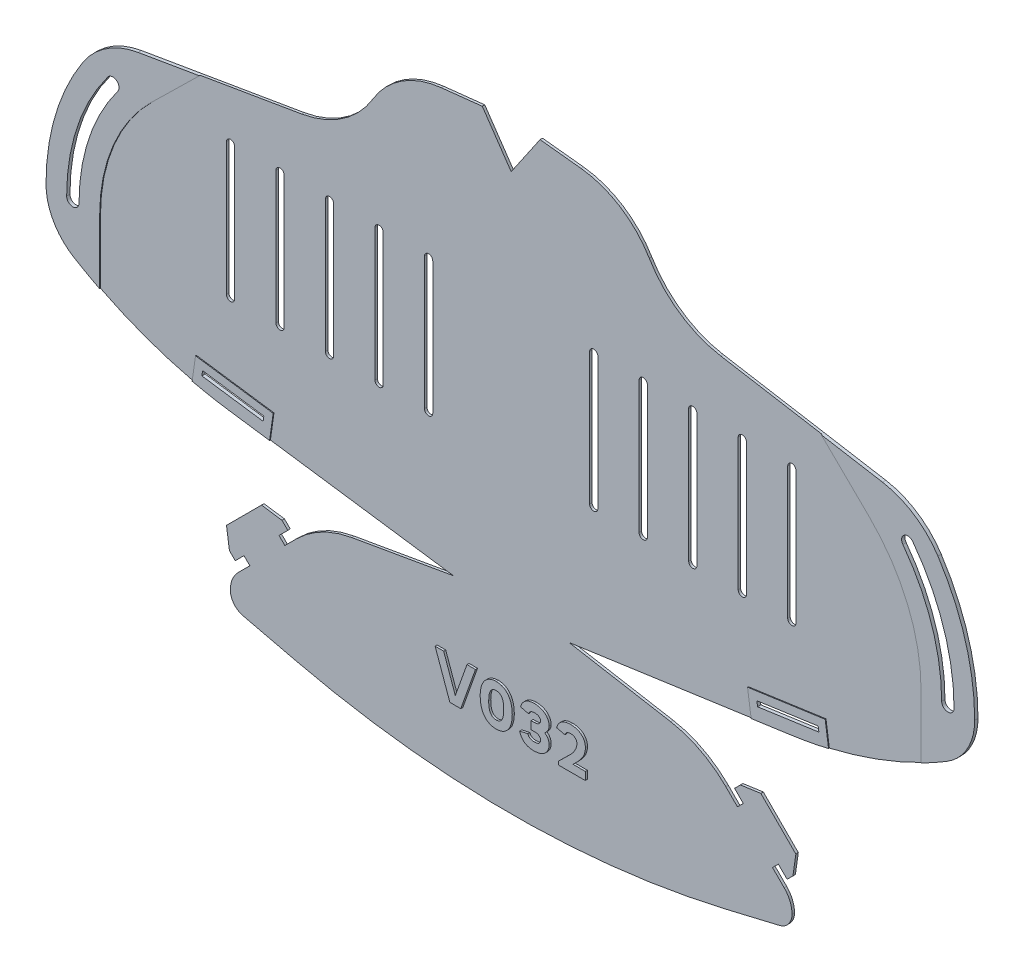
SolidWorks part; units mm, degrees
ref_plane "Front Plane" through (0, 0, 0) normal (0, 0, 1) x (1, 0, 0)
ref_plane "Top Plane" through (0, 0, 0) normal (0, 1, 0) x (1, 0, 0)
ref_plane "Right Plane" through (0, 0, 0) normal (1, 0, 0) x (0, 0, -1)
sketch "Sketch1" plane through (0, 0, 0) normal (0, 0, 1) x (1, 0, 0)
  line L0 (0, 0) -> (0, -145) construction
  line L1 (-14, -102) -> (14, -102) construction
  line L2 (-112.5, -69) -> (112.5, -69) construction
  line L3 (0, -10.2352) -> (-7, 0)
  line L4 (0, -10.2352) -> (7, 0)
  line L5 (7, 0) -> (16.9419, -1.0768)
  line L6 (-90.1804, -30.1909) -> (-50.7439, -23.5)
  line L7 (90.1804, -30.1909) -> (50.7439, -23.5)
  line L8 (-14, -102) -> (-68.2662, -94.2919)
  line L9 (-7, 0) -> (-16.9419, -1.0768)
  line L10 (14, -102) -> (68.2662, -94.2919)
  line L11 (-103.5977, -39) -> (-103.5977, -69) construction
  line L12 (-14, -102) -> (-38.6266, -106.305)
  line L13 (-52, -113.2546) -> (-54.8283, -116.0832)
  line L14 (52, -113.2546) -> (54.8283, -116.0832)
  line L15 (14, -102) -> (38.6266, -106.305)
  line L16 (-54.8283, -116.0832) -> (-56.2426, -114.669)
  line L17 (-56.2426, -114.669) -> (-54.1214, -112.5476)
  line L18 (-54.1214, -112.5476) -> (-55.5356, -111.1334)
  line L19 (-55.5356, -111.1334) -> (-60.4854, -110.4265)
  line L20 (-60.4854, -110.4265) -> (-68.9703, -118.9122)
  line L21 (-64.7275, -123.1546) -> (-63.3132, -124.5688)
  line L22 (-63.3132, -124.5688) -> (-66.1415, -127.3973)
  line L23 (-64.7275, -123.1546) -> (-66.8487, -125.2761)
  line L24 (-66.8487, -125.2761) -> (-68.263, -123.8619)
  line L25 (-68.9703, -118.9122) -> (-68.263, -123.8619)
  line L26 (68.9703, -118.9122) -> (68.263, -123.8619)
  line L27 (66.8487, -125.2761) -> (68.263, -123.8619)
  line L28 (64.7275, -123.1546) -> (66.8487, -125.2761)
  line L29 (63.3132, -124.5688) -> (66.1415, -127.3973)
  line L30 (64.7275, -123.1546) -> (63.3132, -124.5688)
  line L31 (60.4854, -110.4265) -> (68.9703, -118.9122)
  line L32 (55.5356, -111.1334) -> (60.4854, -110.4265)
  line L33 (54.1214, -112.5476) -> (55.5356, -111.1334)
  line L34 (56.2426, -114.669) -> (54.1214, -112.5476)
  line L35 (54.8283, -116.0832) -> (56.2426, -114.669)
  line L36 (-64.9691, -135.8852) -> (-52.4361, -138.8607)
  line L37 (64.9691, -135.8852) -> (52.4361, -138.8607)
  line L38 (-68.9703, -118.9122) -> (-64.7275, -123.1546) construction
  line L39 (-60.4854, -110.4265) -> (-56.2426, -114.669) construction
  arc A0 (-16.9419, -1.0768) -> (-33.4614, -11.6696) centre (-14.5729, -22.9489) ccw
  arc A1 (-33.4614, -11.6696) -> (-50.7439, -23.5) centre (-54.9257, 1.1478) cw
  arc A2 (-103.5977, -39) -> (-90.1804, -30.1909) centre (-86.8349, -49.9091) cw
  arc A3 (-112.5, -69) -> (-103.5977, -39) centre (-57.5, -69) cw
  arc A4 (112.5, -69) -> (103.5977, -39) centre (57.5, -69) ccw
  arc A5 (103.5977, -39) -> (90.1804, -30.1909) centre (86.8349, -49.9091) ccw
  arc A6 (16.9419, -1.0768) -> (33.4614, -11.6696) centre (14.5729, -22.9489) cw
  arc A7 (33.4614, -11.6696) -> (50.7439, -23.5) centre (54.9257, 1.1478) ccw
  arc A8 (-112.5, -69) -> (-105.7111, -81) centre (-98.5, -69) ccw
  arc A9 (-105.7111, -81) -> (-68.2662, -94.2919) centre (-54.2032, 4.7143) ccw
  arc A10 (112.5, -69) -> (105.7111, -81) centre (98.5, -69) cw
  arc A11 (105.7111, -81) -> (68.2662, -94.2919) centre (54.2032, 4.7143) cw
  arc A12 (-38.6266, -106.305) -> (-52, -113.2546) centre (-34.3216, -130.9315) ccw
  arc A13 (38.6266, -106.305) -> (52, -113.2546) centre (34.3216, -130.9315) cw
  arc A14 (-66.1415, -127.3973) -> (-68.0451, -131.9933) centre (-61.5451, -131.9933) ccw
  arc A15 (-68.0451, -131.9933) -> (-64.9691, -135.8852) centre (-64.0451, -131.9933) ccw
  arc A16 (68.0451, -131.9933) -> (64.9691, -135.8852) centre (64.0451, -131.9933) cw
  arc A17 (66.1415, -127.3973) -> (68.0451, -131.9933) centre (61.5451, -131.9933) cw
  arc A19 (-52.4361, -138.8607) -> (0, -145) centre (0, 82) ccw
  arc A20 (52.4361, -138.8607) -> (0, -145) centre (0, 82) cw
  point P8 (0, -102)
  point P11 (0, -69)
  dimension "D5" = 55
  dimension "D11" = 20
  dimension "D13" = 25
  dimension "D16" = 14
  dimension "D15" = 22
  dimension "D18" = 100
  dimension "D22" = 25
  dimension "D31" = 6.5
  dimension "D32" = 4
  dimension "D34" = 227
  dimension "D1" = 145
  dimension "D2" = 28
  dimension "D3" = 43
  dimension "D4" = 76
  dimension "D6" = 225
  dimension "D7" = 14
  dimension "D8" = 12.4
  dimension "D9" = 10
  dimension "D10" = 30
  dimension "D12" = 40
  dimension "D14" = 45.5
  dimension "D17" = 12
  dimension "D19" = 18
  dimension "D20" = 25
  dimension "D21" = 4
  dimension "D23" = 38
  dimension "D24" = 2
  dimension "D25" = 3
  dimension "D26" = 2
  dimension "D27" = 18
  dimension "D29" = 8
  dimension "D30" = 4
extrude "Main Shape" add sketch "Sketch1" along normal blind 0.6
sketch "Sketch2" plane through (0, 0, 0.6) normal (0, 0, 1) x (1, 0, 0)
  line L0 (0, -55) -> (0, 55) construction
  arc A0 (-96.3, -39.9) -> (-106, -69) centre (-57.5, -69) ccw construction
  arc A1 (-97.5, -39) -> (-107.5, -69) centre (-57.5, -69) ccw
  arc A2 (-95.1, -40.8) -> (-104.5, -69) centre (-57.5, -69) ccw
  arc A3 (-95.1, -40.8) -> (-97.5, -39) centre (-96.3, -39.9) ccw
  arc A4 (-107.5, -69) -> (-104.5, -69) centre (-106, -69) ccw
  arc A6 (-103.5977, -39) -> (-112.5, -69) centre (-57.5, -69) ccw construction
  arc A7 (96.3, -39.9) -> (106, -69) centre (57.5, -69) cw construction
  arc A8 (97.5, -39) -> (107.5, -69) centre (57.5, -69) cw
  arc A9 (95.1, -40.8) -> (104.5, -69) centre (57.5, -69) cw
  arc A10 (95.1, -40.8) -> (97.5, -39) centre (96.3, -39.9) cw
  arc A11 (107.5, -69) -> (104.5, -69) centre (106, -69) cw
  point P3 (-103.5111, -53.663)
  point P19 (103.5111, -53.663)
  dimension "D1" = 5
  dimension "D2" = 1.5
extrude "Elastic Attachment Points" cut sketch "Sketch2" against normal through all
sketch "Sketch7" plane through (0, 0, 0.6) normal (0, 0, 1) x (1, 0, 0)
  line L0 (-99.5, -69) -> (-99.5, -84.4384)
  line L1 (-86.8939, -39) -> (-75.3319, -27.6717)
  line L2 (-50.7439, -23.5) -> (-90.1804, -30.1909) construction
  line L3 (-75.3319, -27.6717) -> (-90.1804, -30.1909)
  line L4 (0, -55) -> (0, 55) construction
  line L5 (75.3319, -27.6717) -> (90.1804, -30.1909)
  line L6 (86.8939, -39) -> (75.3319, -27.6717)
  line L7 (99.5, -69) -> (99.5, -84.4384)
  arc A0 (-99.5, -69) -> (-86.8939, -39) centre (-57.5, -69) cw
  arc A1 (-95.1, -40.8) -> (-104.5, -69) centre (-57.5, -69) ccw construction
  arc A2 (-105.7111, -81) -> (-68.2662, -94.2919) centre (-54.2032, 4.7143) ccw construction
  arc A3 (-112.5, -69) -> (-105.7111, -81) centre (-98.5, -69) ccw construction
  arc A4 (-103.5977, -39) -> (-112.5, -69) centre (-57.5, -69) ccw construction
  arc A5 (-90.1804, -30.1909) -> (-103.5977, -39) centre (-86.8349, -49.9091) ccw construction
  arc A6 (-105.7111, -81) -> (-99.5, -84.4384) centre (-54.2032, 4.7143) ccw
  arc A7 (-112.5, -69) -> (-105.7111, -81) centre (-98.5, -69) ccw
  arc A8 (-103.5977, -39) -> (-112.5, -69) centre (-57.5, -69) ccw
  arc A9 (-90.1804, -30.1909) -> (-103.5977, -39) centre (-86.8349, -49.9091) ccw
  arc A10 (90.1804, -30.1909) -> (103.5977, -39) centre (86.8349, -49.9091) cw
  arc A11 (103.5977, -39) -> (112.5, -69) centre (57.5, -69) cw
  arc A12 (112.5, -69) -> (105.7111, -81) centre (98.5, -69) cw
  arc A13 (105.7111, -81) -> (99.5, -84.4384) centre (54.2032, 4.7143) cw
  arc A14 (99.5, -69) -> (86.8939, -39) centre (57.5, -69) ccw
  arc A15 (-107.5, -69) -> (-104.5, -69) centre (-106, -69) ccw construction
  arc A16 (-95.1, -40.8) -> (-97.5, -39) centre (-96.3, -39.9) ccw construction
  arc A17 (-97.5, -39) -> (-107.5, -69) centre (-57.5, -69) ccw construction
  arc A18 (-107.5, -69) -> (-104.5, -69) centre (-106, -69) ccw
  arc A19 (-95.1, -40.8) -> (-97.5, -39) centre (-96.3, -39.9) ccw
  arc A20 (-95.1, -40.8) -> (-104.5, -69) centre (-57.5, -69) ccw
  arc A21 (-97.5, -39) -> (-107.5, -69) centre (-57.5, -69) ccw
  arc A22 (104.5, -69) -> (107.5, -69) centre (106, -69) ccw construction
  arc A23 (97.5, -39) -> (95.1, -40.8) centre (96.3, -39.9) ccw construction
  arc A24 (104.5, -69) -> (95.1, -40.8) centre (57.5, -69) ccw construction
  arc A25 (107.5, -69) -> (97.5, -39) centre (57.5, -69) ccw construction
  arc A26 (104.5, -69) -> (107.5, -69) centre (106, -69) ccw
  arc A27 (97.5, -39) -> (95.1, -40.8) centre (96.3, -39.9) ccw
  arc A28 (104.5, -69) -> (95.1, -40.8) centre (57.5, -69) ccw
  arc A29 (107.5, -69) -> (97.5, -39) centre (57.5, -69) ccw
  dimension "D1" = 5
extrude "Reinforced Attachment Points" add sketch "Sketch7" along normal blind 0.2
sketch "Sketch6" plane through (0, 0, 0.6) normal (0, 0, 1) x (1, 0, 0)
  line L0 (-74.7442, -90.3417) -> (-59.8932, -92.4511)
  line L1 (-59.8932, -92.4511) -> (-59.7245, -91.2631)
  line L2 (-59.7245, -91.2631) -> (-74.5754, -89.1536)
  line L3 (-74.5754, -89.1536) -> (-74.7442, -90.3417)
  line L4 (-68.2662, -94.2919) -> (-14, -102) construction
  line L5 (-67.1499, -90.2083) -> (-67.3187, -91.3964) construction
  line L13 (0, -55) -> (0, 55) construction
  line L14 (67.1499, -90.2083) -> (67.3187, -91.3964) construction
  line L15 (74.7442, -90.3417) -> (74.5754, -89.1536)
  line L16 (59.7245, -91.2631) -> (59.8932, -92.4511)
  line L22 (59.7245, -91.2631) -> (74.5754, -89.1536)
  line L24 (74.7442, -90.3417) -> (59.8932, -92.4511)
  dimension "D1" = 3
  dimension "D2" = 15
  dimension "D3" = 54.28
  dimension "D4" = 1.2
extrude "Tab Slits" cut sketch "Sketch6" against normal through all
sketch "Sketch9" plane through (0, 0, 0.6) normal (0, 0, 1) x (1, 0, 0)
  line L4 (-59.8932, -92.4511) -> (-59.7245, -91.2631) construction
  line L5 (-74.7442, -90.3417) -> (-59.8932, -92.4511) construction
  line L6 (-74.5754, -89.1536) -> (-74.7442, -90.3417) construction
  line L7 (-59.7245, -91.2631) -> (-74.5754, -89.1536) construction
  line L12 (-59.8932, -92.4511) -> (-59.7245, -91.2631)
  line L13 (-74.7442, -90.3417) -> (-59.8932, -92.4511)
  line L14 (-74.5754, -89.1536) -> (-74.7442, -90.3417)
  line L15 (-59.7245, -91.2631) -> (-74.5754, -89.1536)
  line L16 (-58.335, -95.7026) -> (-57.4631, -89.5642)
  line L17 (-68.2662, -94.2919) -> (-14, -102) construction
  line L18 (-57.4631, -89.5642) -> (-76.2743, -86.8922)
  line L19 (-76.2743, -86.8922) -> (-77.0895, -92.6316)
  line L20 (-68.2662, -94.2919) -> (-58.335, -95.7026)
  line L21 (0, -55) -> (0, 55) construction
  line L22 (68.2662, -94.2919) -> (58.335, -95.7026)
  line L23 (76.2743, -86.8922) -> (77.0895, -92.6316)
  line L24 (57.4631, -89.5642) -> (76.2743, -86.8922)
  line L25 (58.335, -95.7026) -> (57.4631, -89.5642)
  line L26 (59.7245, -91.2631) -> (74.5754, -89.1536)
  line L27 (74.5754, -89.1536) -> (74.7442, -90.3417)
  line L28 (74.7442, -90.3417) -> (59.8932, -92.4511)
  line L29 (59.8932, -92.4511) -> (59.7245, -91.2631)
  arc A0 (-99.5, -84.4384) -> (-68.2662, -94.2919) centre (-54.2032, 4.7143) ccw construction
  arc A1 (-77.0895, -92.6316) -> (-68.2662, -94.2919) centre (-54.2032, 4.7143) ccw
  arc A2 (77.0895, -92.6316) -> (68.2662, -94.2919) centre (54.2032, 4.7143) cw
  dimension "D1" = 2
  dimension "D2" = 2
  dimension "D3" = 2
extrude "Reinforced Tab Slits" add sketch "Sketch9" along normal blind 0.2
sketch "Sketch3" plane through (0, 0, 0.6) normal (0, 0, 1) x (1, 0, 0)
  line L0 (-20, -38.45) -> (-20, -70.45) construction
  line L1 (-19, -38.45) -> (-19, -70.45)
  line L2 (-21, -38.45) -> (-21, -70.45)
  line L3 (0, -10.2352) -> (0, -145) construction
  line L4 (-106, -69) -> (-96.3, -69) construction
  line L5 (-96.3, -69) -> (-96.3, -39.9) construction
  line L6 (-32, -38.45) -> (-32, -70.45) construction
  line L7 (-31, -38.45) -> (-31, -70.45)
  line L8 (-33, -38.45) -> (-33, -70.45)
  line L9 (-44, -38.45) -> (-44, -70.45) construction
  line L10 (-43, -38.45) -> (-43, -70.45)
  line L11 (-45, -38.45) -> (-45, -70.45)
  line L12 (-56, -38.45) -> (-56, -70.45) construction
  line L13 (-55, -38.45) -> (-55, -70.45)
  line L14 (-57, -38.45) -> (-57, -70.45)
  line L15 (-68, -38.45) -> (-68, -70.45) construction
  line L16 (-67, -38.45) -> (-67, -70.45)
  line L17 (-69, -38.45) -> (-69, -70.45)
  line L18 (20, -38.45) -> (20, -70.45) construction
  line L19 (19, -38.45) -> (19, -70.45)
  line L20 (21, -38.45) -> (21, -70.45)
  line L21 (32, -38.45) -> (32, -70.45) construction
  line L22 (31, -38.45) -> (31, -70.45)
  line L23 (33, -38.45) -> (33, -70.45)
  line L24 (44, -38.45) -> (44, -70.45) construction
  line L25 (43, -38.45) -> (43, -70.45)
  line L26 (45, -38.45) -> (45, -70.45)
  line L27 (56, -38.45) -> (56, -70.45) construction
  line L28 (55, -38.45) -> (55, -70.45)
  line L29 (57, -38.45) -> (57, -70.45)
  line L30 (68, -38.45) -> (68, -70.45) construction
  line L31 (67, -38.45) -> (67, -70.45)
  line L32 (69, -38.45) -> (69, -70.45)
  arc A0 (-19, -38.45) -> (-21, -38.45) centre (-20, -38.45) ccw
  arc A1 (-21, -70.45) -> (-19, -70.45) centre (-20, -70.45) ccw
  arc A2 (-52.4361, -138.8607) -> (52.4361, -138.8607) centre (0, 82) ccw construction
  arc A3 (-31, -38.45) -> (-33, -38.45) centre (-32, -38.45) ccw
  arc A4 (-33, -70.45) -> (-31, -70.45) centre (-32, -70.45) ccw
  arc A5 (-43, -38.45) -> (-45, -38.45) centre (-44, -38.45) ccw
  arc A6 (-45, -70.45) -> (-43, -70.45) centre (-44, -70.45) ccw
  arc A7 (-55, -38.45) -> (-57, -38.45) centre (-56, -38.45) ccw
  arc A8 (-57, -70.45) -> (-55, -70.45) centre (-56, -70.45) ccw
  arc A9 (-67, -38.45) -> (-69, -38.45) centre (-68, -38.45) ccw
  arc A10 (-69, -70.45) -> (-67, -70.45) centre (-68, -70.45) ccw
  arc A11 (19, -38.45) -> (21, -38.45) centre (20, -38.45) cw
  arc A12 (21, -70.45) -> (19, -70.45) centre (20, -70.45) cw
  arc A13 (31, -38.45) -> (33, -38.45) centre (32, -38.45) cw
  arc A14 (33, -70.45) -> (31, -70.45) centre (32, -70.45) cw
  arc A15 (43, -38.45) -> (45, -38.45) centre (44, -38.45) cw
  arc A16 (45, -70.45) -> (43, -70.45) centre (44, -70.45) cw
  arc A17 (55, -38.45) -> (57, -38.45) centre (56, -38.45) cw
  arc A18 (57, -70.45) -> (55, -70.45) centre (56, -70.45) cw
  arc A19 (67, -38.45) -> (69, -38.45) centre (68, -38.45) cw
  arc A20 (69, -70.45) -> (67, -70.45) centre (68, -70.45) cw
  point P2 (-20, -54.45)
  point P13 (-19, -54.45)
  point P16 (-96.3, -54.45)
  point P20 (-32, -54.45)
  point P31 (-44, -54.45)
  point P38 (-56, -54.45)
  point P45 (-68, -54.45)
  point P52 (20, -54.45)
  point P59 (32, -54.45)
  point P66 (44, -54.45)
  point P73 (56, -54.45)
  point P80 (68, -54.45)
  dimension "D1" = 2
  dimension "D2" = 32
  dimension "D3" = 20
  dimension "D4" = 5
  dimension "D5" = 10
extrude "Breathing Slits" cut sketch "Sketch3" against normal through all
sketch "Sketch8" plane through (0, 0, 0.6) normal (0, 0, 1) x (1, 0, 0)
  line L0 (-67.0266, -128.5) -> (67.0266, -128.5) construction
  line L1 (0, -10.2352) -> (0, -145) construction
  arc A0 (-52.4361, -138.8607) -> (52.4361, -138.8607) centre (0, 82) ccw construction
  arc A1 (-66.1415, -127.3973) -> (-68.0451, -131.9933) centre (-61.5451, -131.9933) ccw construction
  text T0 "<b>V032</b>" font "Double Porter 3" height 10
  point P9 (0, -128.5)
  dimension "D2" = 16.5
extrude "Version Number" add sketch "Sketch8" along normal blind 0.5
